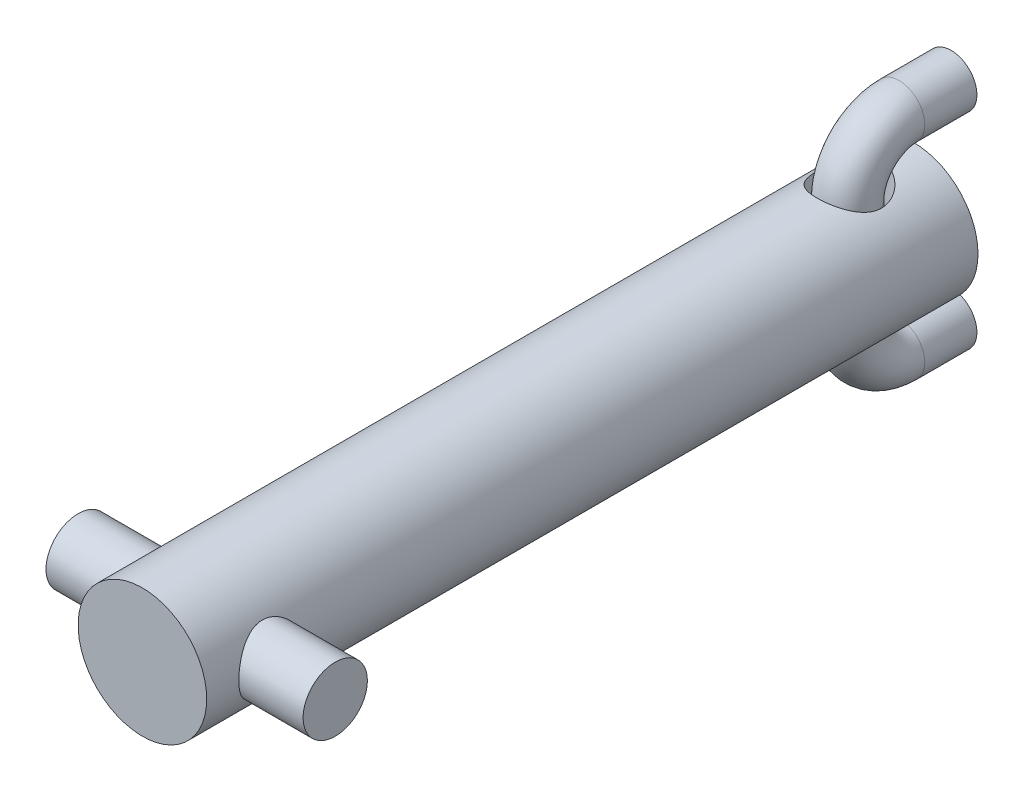
SolidWorks part; units mm, degrees
ref_plane "Front Plane" through (0, 0, 0) normal (0, 0, 1) x (1, 0, 0)
ref_plane "Top Plane" through (0, 0, 0) normal (0, 1, 0) x (1, 0, 0)
ref_plane "Right Plane" through (0, 0, 0) normal (1, 0, 0) x (0, 0, -1)
sketch "Sketch1" plane through (0, 0, 0) normal (0, 0, 1) x (1, 0, 0)
  circle A0 centre (0, 0) radius 3.175
  dimension "D1" = 6.35
extrude "Boss-Extrude1" add sketch "Sketch1" along normal blind 38.1
sketch "Sketch2" plane through (0, 0, 0) normal (0, 1, 0) x (1, 0, 0)
  circle A0 centre (0, -3.175) radius 1.5875
  dimension "D2" = 3.175
  dimension "D1" = 3.175
extrude "Cut-Extrude1" cut sketch "Sketch2" against normal mid plane 31.75
sketch "Sketch3" plane through (0, 0, 0) normal (1, 0, 0) x (0, 0, -1)
  line L0 (-38.1, 3.175) -> (-38.1, -3.175) construction
  circle A0 centre (-34.925, 0) radius 1.5875
  dimension "D1" = 3.175
  dimension "D2" = 3.175
  dimension "D3" = 3.175
extrude "Boss-Extrude2" add sketch "Sketch3" along normal mid plane 12.7
sketch "Sketch4" plane through (0, 0, 0) normal (1, 0, 0) x (0, 0, -1)
  line L0 (-3.263, -2.6975) -> (-3.263, 2.3825)
  line L1 (-0.723, 4.9225) -> (1.8504, 4.9225)
  line L2 (-0.723, -5.2375) -> (1.8504, -5.2375)
  arc A0 (-3.263, -2.6975) -> (-0.723, -5.2375) centre (-0.723, -2.6975) ccw
  arc A1 (-0.723, 4.9225) -> (-3.263, 2.3825) centre (-0.723, 2.3825) ccw
  point P3 (-3.263, -0.1575)
  point P7 (-3.263, -5.2375)
  point P10 (-3.263, 4.9225)
  dimension "D2" = 2.54
  dimension "D1" = 10.16
  dimension "D3" = 1.8504
  dimension "D4" = 3.263
  dimension "D5" = 4.9225
sweep "Sweep1" add path "Sketch4" circular profile diameter 2.54 parameters "D3"=2.54
